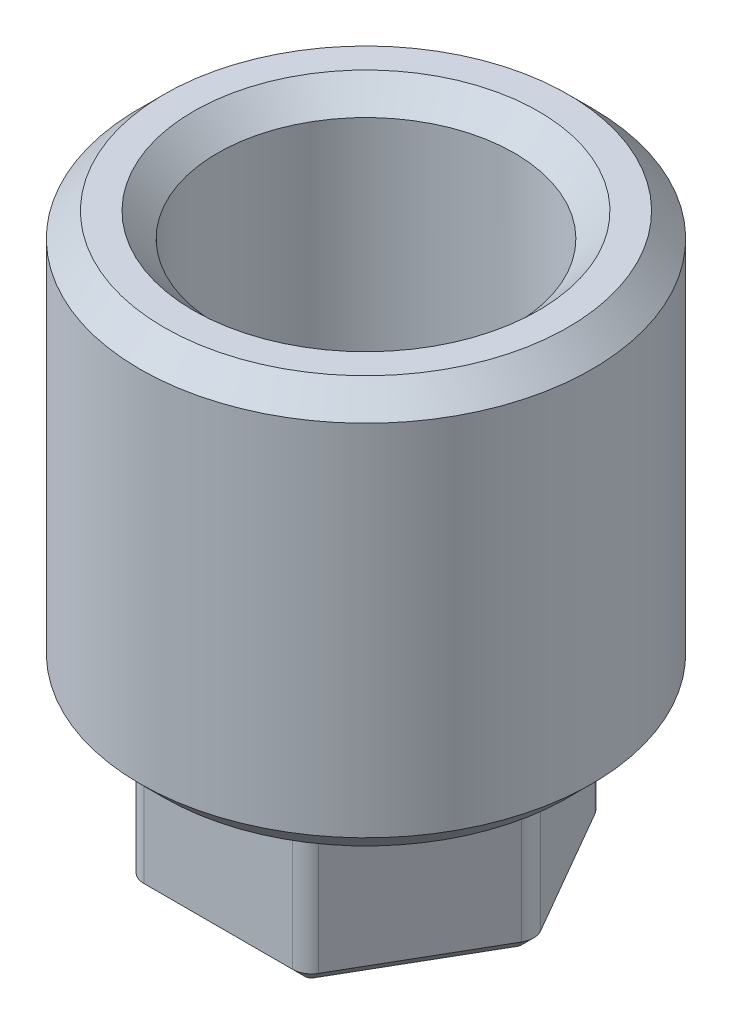
SolidWorks part; units mm, degrees
ref_plane "Front" through (0, 0, 0) normal (0, 0, 1) x (1, 0, 0)
ref_plane "Top" through (0, 0, 0) normal (0, 1, 0) x (1, 0, 0)
ref_plane "Right" through (0, 0, 0) normal (1, 0, 0) x (0, 0, -1)
sketch "Sketch1" plane through (0, 0, 0) normal (0, 1, 0) x (1, 0, 0)
  line L1 (1.7964, 3.1115) -> (-1.7964, 3.1115)
  line L2 (-1.7964, 3.1115) -> (-3.5929, 0)
  line L3 (-3.5929, 0) -> (-1.7964, -3.1115)
  line L4 (-1.7964, -3.1115) -> (1.7964, -3.1115)
  line L5 (1.7964, -3.1115) -> (3.5929, 0)
  line L6 (3.5929, 0) -> (1.7964, 3.1115)
  circle A0 centre (0, 0) radius 3.1115 construction
  dimension "D1" = 6.223
extrude "Boss-Extrude1" add sketch "Sketch1" along normal blind 3.175
sketch "Sketch2" plane through (0, 3.175, 0) normal (0, 1, 0) x (1, 0, 0)
  circle A0 centre (0, 0) radius 4.7625
  dimension "D1" = 9.525
extrude "Boss-Extrude2" add sketch "Sketch2" along normal blind 2.2301
sketch "Sketch3" plane through (0, 5.4051, 0) normal (0, 1, 0) x (1, 0, 0)
  circle A0 centre (0, 0) radius 3.127
  circle A1 centre (0, 0) radius 4.7625 construction
  circle A2 centre (0, 0) radius 4.7625
  dimension "D1" = 6.254
extrude "Boss-Extrude3" add sketch "Sketch3" along normal blind 6.35
sketch "Sketch4" plane through (0, 5.4051, 0) normal (0, 1, 0) x (1, 0, 0)
  line L0 (-3.0944, 0.45) -> (3.0944, 0.45)
  line L1 (-3.0944, -0.45) -> (3.0944, -0.45)
  line L2 (0, -0.45) -> (0, 0.45) construction
  circle A0 centre (0, 0) radius 3.127 construction
  arc A1 (3.0944, -0.45) -> (3.0944, 0.45) centre (0, 0) ccw
  arc A2 (-3.0944, 0.45) -> (-3.0944, -0.45) centre (0, 0) ccw
  dimension "D1" = 0.9
extrude "Boss-Extrude4" add sketch "Sketch4" along normal blind 1.5
fillet "Fillet1" radius 0.3969 20 edges at (1.7964, 1.5875, 3.1115) (-1.7964, 1.5875, 3.1115) (-3.5929, 1.5875, 0) (-1.7964, 1.5875, -3.1115) (3.5929, 1.5875, 0) (1.7964, 1.5875, -3.1115) (0, 3.175, 3.1115) (-2.6946, 3.175, 1.5558) (-2.6946, 3.175, -1.5557) (2.6946, 3.175, -1.5557) (2.6946, 3.175, 1.5557) (0, 3.175, -3.1115) (-3.0944, 6.1551, -0.45) (-3.0944, 6.1551, 0.45) (0, 5.4051, -0.45) (0, 5.4051, -3.127) (3.0944, 6.1551, -0.45) (0, 5.4051, 0.45) (3.0944, 6.1551, 0.45) (0, 5.4051, 3.127)
chamfer "Chamfer1" distance 0.508 angle 45 3 edges at (0, 11.7551, 3.127) (0, 11.7551, 4.7625) (0, 3.175, 4.7625)
chamfer "Chamfer2" distance 0.127 angle 45 6 edges at (-2.9167, 6.9051, 0.6138) (2.9167, 6.9051, 0.6138) (0, 6.9051, 0.45) (2.9167, 6.9051, -0.6138) (-2.9167, 6.9051, -0.6138) (0, 6.9051, -0.45)
chamfer "Chamfer3" distance 0.254 angle 45 12 edges at (3.5315, 0, 0) (2.6946, 0, -1.5557) (1.7657, 0, -3.0583) (0, 0, -3.1115) (-1.7657, 0, -3.0583) (-2.6946, 0, -1.5557) (-3.5315, 0, 0) (-2.6946, 0, 1.5558) (-1.7657, 0, 3.0583) (0, 0, 3.1115) (1.7657, 0, 3.0583) (2.6946, 0, 1.5557)
